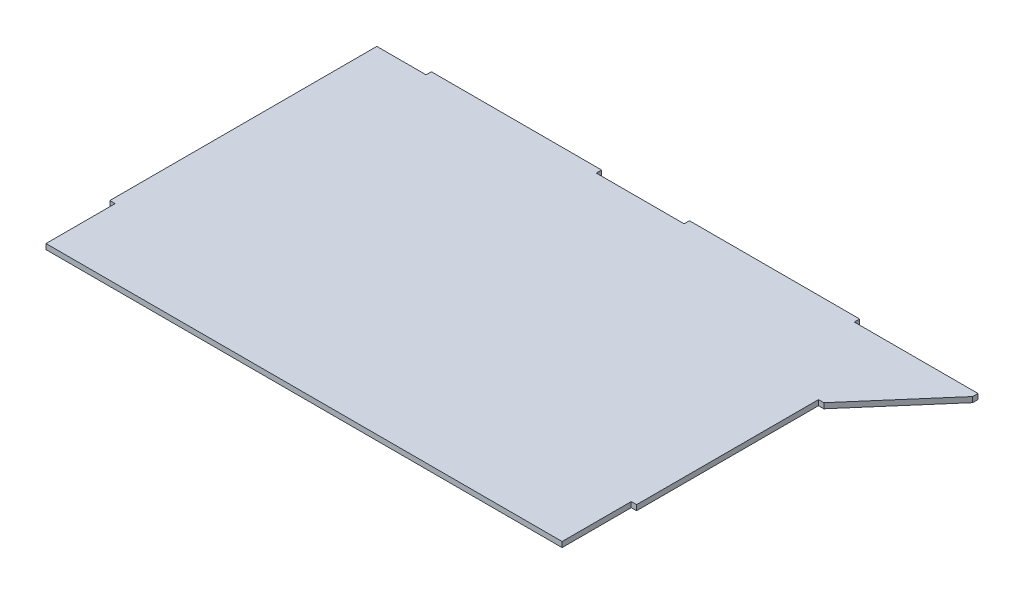
SolidWorks part; units mm, degrees
material "6061-T6 (SS)"
ref_plane "X-Y Datum" through (0, 0, 0) normal (0, 0, 1) x (1, 0, 0)
ref_plane "X-Z Datum" through (0, 0, 0) normal (0, 1, 0) x (1, 0, 0)
ref_plane "Y-Z Datum" through (0, 0, 0) normal (1, 0, 0) x (0, 0, -1)
sketch "Sketch1" plane through (0, 0, 0) normal (0, 0, 1) x (1, 0, 0)
  line L1 (-157.2158, -1.5875) -> (157.2158, -1.5875)
  line L2 (-157.2158, -1.5875) -> (-157.2158, 1.5875)
  line L3 (-157.2158, 1.5875) -> (157.2158, 1.5875)
  line L4 (157.2158, -1.5875) -> (157.2158, 1.5875)
  line L5 (-157.2158, -1.5875) -> (157.2158, 1.5875) construction
  line L6 (-157.2158, 1.5875) -> (157.2158, -1.5875) construction
  point P0 (0, 0)
  dimension "D1" = 314.4317
  dimension "D2" = 3.175
extrude "Boss-Extrude1" add sketch "Sketch1" along normal blind 200.6618
sketch "Sketch5" plane through (0, 1.5875, 0) normal (0, 1, 0) x (1, 0, 0)
  line L0 (-153.9646, -200.738) -> (-153.9646, -159.3106)
  line L1 (-157.2158, -200.6618) -> (-154.0408, -200.6618)
  line L2 (-157.292, -159.3106) -> (-153.9646, -159.3106)
  line L3 (-157.2158, -200.6618) -> (-157.2158, -159.3868)
  line L4 (-157.292, -200.738) -> (-157.292, -159.3106)
  line L5 (-157.2158, -159.3868) -> (-154.0408, -159.3868)
  line L6 (-154.0408, -200.6618) -> (-154.0408, -159.3868)
  line L7 (-157.292, -200.738) -> (-153.9646, -200.738)
  line M11 (-157.2158, 0) -> (-157.2158, -200.6618)
  line M12 (-157.2158, -200.6618) -> (157.2158, -200.6618)
  dimension "D1" = 41.275
  dimension "D2" = 3.175
  dimension "D3" = 0.0762
extrude "Cut-Extrude2" cut sketch "Sketch5" against normal blind 3.175 and the other way through all contours L6 L5 M12 M11 region at (-155.6283, 1.5875, 180.0243)
mirror "Mirror1" about plane through (0, 0, 0) normal (1, 0, 0) of "Cut-Extrude2"
sketch "Sketch6" plane through (0, 1.5875, 0) normal (0, 1, 0) x (1, 0, 0)
  line L6 (-157.2158, -180.3418) -> (-81.0158, -180.3418)
  line L7 (-157.2158, -180.3418) -> (-157.2158, -200.6618)
  line L8 (-157.2158, -200.6618) -> (-81.0158, -200.6618)
  line L9 (-81.0158, -180.3418) -> (-81.0158, -200.6618)
  line L10 (154.0408, -200.6618) -> (-154.0408, -200.6618) construction
  line L11 (-157.2158, -159.3868) -> (-157.2158, 0) construction
  line L13 (154.0408, -200.6618) -> (-81.0158, -200.6618)
  line L14 (154.0408, -200.6618) -> (154.0408, -180.3418)
  line L15 (154.0408, -180.3418) -> (-81.0158, -180.3418)
  line L16 (-81.0158, -200.6618) -> (-81.0158, -180.3418)
  line M18 (-154.0408, -159.3868) -> (-154.0408, -200.6618)
  line M19 (-154.0408, -200.6618) -> (154.0408, -200.6618)
  dimension "D1" = 76.2
  dimension "D2" = 20.32
extrude "Cut-Extrude4" [suppressed] cut sketch "Sketch6" against normal through all contours L9 L6 M18 M19
sketch "Sketch7" [suppressed] plane through (0, 1.5875, 0) normal (0, 1, 0) x (1, 0, 0)
  line L1 (-81.2823, -215.455) -> (155.1963, -215.455)
  line L2 (-81.2823, -215.455) -> (-81.2823, -235.775)
  line L3 (-81.2823, -235.775) -> (155.1963, -235.775)
  line L4 (155.1963, -215.455) -> (155.1963, -235.775)
extrude "Cut-Extrude5" [suppressed] cut sketch "Sketch7" against normal through all
sketch "Sketch8" [suppressed] plane through (0, 1.5875, 0) normal (0, 1, 0) x (1, 0, 0)
  line L0 (154.0408, -200.6618) -> (-154.0408, -200.6618) construction
  line L1 (157.2158, -180.3418) -> (81.0158, -180.3418)
  line L2 (157.2158, -180.3418) -> (157.2158, -200.6618)
  line L3 (157.2158, -200.6618) -> (81.0158, -200.6618)
  line L4 (81.0158, -180.3418) -> (81.0158, -200.6618)
  line L5 (157.2158, -159.3868) -> (157.2158, 0) construction
  dimension "D1" = 20.32
  dimension "D2" = 76.2
extrude "Cut-Extrude6" [suppressed] cut sketch "Sketch8" against normal through all
sketch "Sketch9" [suppressed] plane through (0, 0, 215.455) normal (0, 0, 1) x (1, 0, 0)
  line L4 (155.1963, 1.5875) -> (-155.1963, 1.5875)
  line L5 (-155.1963, 1.5875) -> (-155.1963, -1.5875)
  line L6 (-155.1963, -1.5875) -> (155.1963, -1.5875)
  line L7 (155.1963, -1.5875) -> (155.1963, 1.5875)
  line L8 (155.1963, 1.5875) -> (-155.1963, 1.5875)
  line L9 (-155.1963, 1.5875) -> (-155.1963, -1.5875)
  line L10 (-155.1963, -1.5875) -> (155.1963, -1.5875)
  line L11 (155.1963, -1.5875) -> (155.1963, 1.5875)
  dimension "D1" = 0
extrude "Cut-Extrude7" [suppressed] cut sketch "Sketch9" against normal blind 11.68
sketch "Sketch10" plane through (0, -1.5875, 0) normal (0, -1, 0) x (1, 0, 0)
  line L2 (201.6506, 0) -> (201.6506, 3.175)
  line L8 (157.2158, 0) -> (201.6506, 0)
  line L10 (157.2158, 159.3868) -> (157.2158, 0) construction
  line L11 (157.2158, 50.8) -> (157.2158, 0)
  line L12 (157.2158, 50.8) -> (160.3908, 50.8)
  line L13 (160.3908, 50.8) -> (201.6506, 3.175)
  dimension "D1" = 50.8
  dimension "D2" = 44.4348
  dimension "D3" = 3.175
  dimension "D4" = 3.175
extrude "Boss-Extrude3" add sketch "Sketch10" against normal blind 3.175
sketch "Sketch12" plane through (0, 0, 0) normal (0, 0, -1) x (-1, 0, 0)
  line L0 (-77.0205, 1.6637) -> (-77.0205, -1.6637) construction
  line L1 (157.2158, -1.5875) -> (-201.6506, -1.5875) construction
  line L2 (-127.8205, 1.5875) -> (-26.2205, 1.5875)
  line L3 (-127.8205, 1.5875) -> (-127.8205, -1.5875)
  line L4 (-127.8205, -1.5875) -> (-26.2205, -1.5875)
  line L5 (-26.2205, 1.5875) -> (-26.2205, -1.5875)
  line L6 (-127.8205, 1.5875) -> (-26.2205, -1.5875) construction
  line L7 (-127.8205, -1.5875) -> (-26.2205, 1.5875) construction
  point P0 (-77.0205, -1.6637)
  point P1 (-77.0205, 1.6637)
  point P4 (-77.0205, 0)
  dimension "D1" = 101.6
extrude "Boss-Extrude5" add sketch "Sketch12" along normal blind 3.175
mirror "Mirror2" about plane through (0, 0, 0) normal (1, 0, 0) of "Boss-Extrude5"
